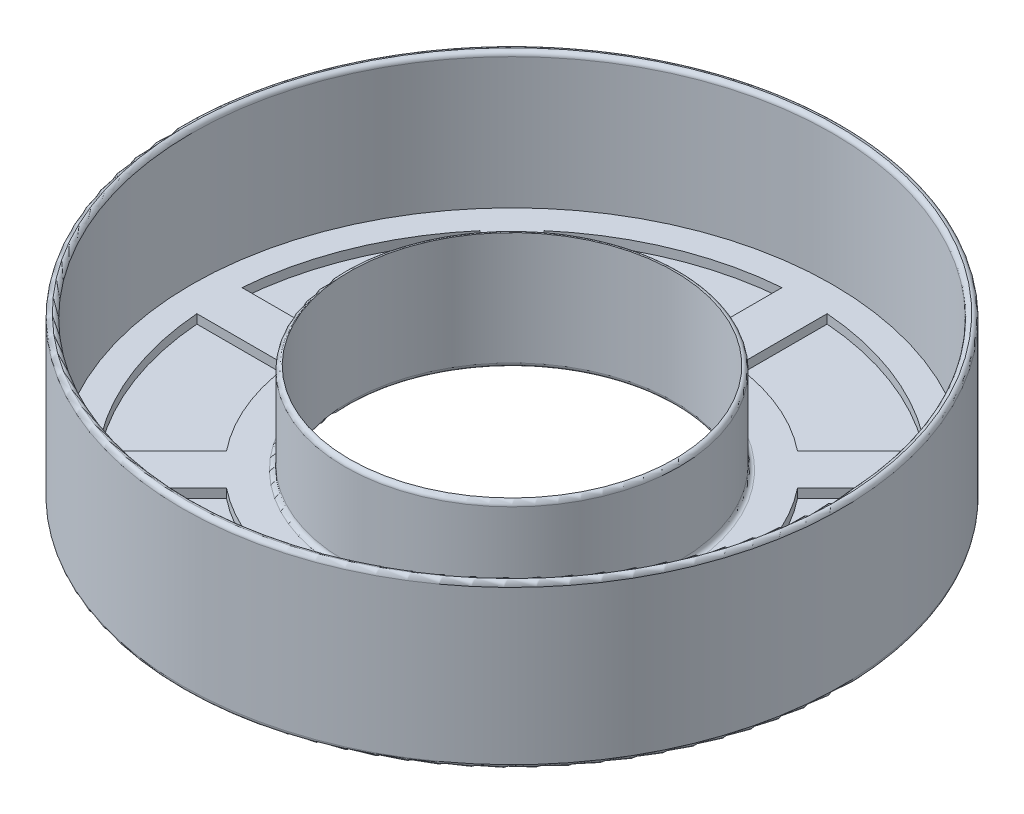
SolidWorks part; units mm, degrees
ref_plane "Front Plane" through (0, 0, 0) normal (0, 0, 1) x (1, 0, 0)
ref_plane "Top Plane" through (0, 0, 0) normal (0, 1, 0) x (1, 0, 0)
ref_plane "Right Plane" through (0, 0, 0) normal (1, 0, 0) x (0, 0, -1)
sketch "Sketch2" plane through (0, 0, 0) normal (0, 1, 0) x (1, 0, 0)
  circle A0 centre (0, 0) radius 18
  circle A1 centre (0, 0) radius 36.5
  dimension "D1" = 73
  dimension "D2" = 36
extrude "Boss-Extrude1" add sketch "Sketch2" along normal blind 3
sketch "Sketch3" plane through (0, 3, 0) normal (0, 1, 0) x (1, 0, 0)
  circle A0 centre (0, 0) radius 35.5
  circle A1 centre (0, 0) radius 19
  circle M3 centre (0, 0) radius 36.5
extrude "Boss-Extrude2" add sketch "Sketch3" along normal blind 15 contours A0 M3 region at (-36.3968, 3, 0)
sketch "Sketch4" plane through (0, 3, 0) normal (0, 1, 0) x (1, 0, 0)
  circle A0 centre (0, 0) radius 18.5
  circle M3 centre (0, 0) radius 18
extrude "Boss-Extrude3" add sketch "Sketch4" along normal blind 10 contours A0 M3 region at (-18.4477, 3, 0)
fillet "Fillet1" radius 0.5 6 edges at (0, 3, 18.5) (0, 13, 18.5) (0, 18, 35.5) (0, 18, 36.5) (0, 0, 18) (0, 0, 36.5)
sketch "Sketch5" plane through (0, 3, 0) normal (0, 1, 0) x (1, 0, 0)
  line L19 (14.0436, 17.5792) -> (21.1451, 24.6806)
  line L21 (-2.5, 22.3607) -> (-2.5, 32.4037)
  line L22 (-14.0436, 17.5792) -> (-21.1451, 24.6806)
  line L25 (-14.0436, -17.5792) -> (-21.1451, -24.6806)
  line L27 (2.5, -22.3607) -> (2.5, -32.4037)
  line L28 (14.0436, -17.5792) -> (21.1451, -24.6806)
  line L35 (-22.3607, -2.5) -> (-32.4037, -2.5)
  line L37 (22.3607, 2.5) -> (32.4037, 2.5)
  line L39 (24.6806, 21.1451) -> (17.5792, 14.0436)
  line L41 (32.4037, -2.5) -> (22.3607, -2.5)
  line L42 (2.5, 32.4037) -> (2.5, 22.3607)
  line L45 (-24.6806, 21.1451) -> (-17.5792, 14.0436)
  line L46 (-32.4037, 2.5) -> (-22.3607, 2.5)
  line L47 (15.9099, 15.9099) -> (22.981, 22.981)
  line L48 (-24.6806, -21.1451) -> (-17.5792, -14.0436)
  line L49 (-32.5, 0) -> (-22.5, 0) construction
  line L50 (-2.5, -32.4037) -> (-2.5, -22.3607)
  line L51 (22.5, 0) -> (32.5, 0) construction
  line L52 (24.6806, -21.1451) -> (17.5792, -14.0436)
  line L53 (-22.981, 22.981) -> (-15.9099, 15.9099)
  line L54 (0, 32.5) -> (0, 22.5) construction
  line L61 (-15.9099, -15.9099) -> (-22.981, -22.981)
  line L62 (0, -22.5) -> (0, -32.5) construction
  line L63 (15.9099, -15.9099) -> (22.981, -22.981)
  arc A2 (-2.5, 32.4037) -> (-21.1451, 24.6806) centre (0, 0) ccw
  arc A3 (-2.5, 22.3607) -> (-14.0436, 17.5792) centre (0, 0) ccw
  arc A8 (14.0436, 17.5792) -> (2.5, 22.3607) centre (0, 0) ccw
  arc A13 (21.1451, 24.6806) -> (2.5, 32.4037) centre (0, 0) ccw
  arc A14 (22.3607, 2.5) -> (17.5792, 14.0436) centre (0, 0) ccw
  arc A19 (32.4037, 2.5) -> (24.6806, 21.1451) centre (0, 0) ccw
  arc A20 (17.5792, -14.0436) -> (22.3607, -2.5) centre (0, 0) ccw
  arc A25 (24.6806, -21.1451) -> (32.4037, -2.5) centre (0, 0) ccw
  arc A26 (2.5, -22.3607) -> (14.0436, -17.5792) centre (0, 0) ccw
  arc A31 (2.5, -32.4037) -> (21.1451, -24.6806) centre (0, 0) ccw
  arc A32 (-14.0436, -17.5792) -> (-2.5, -22.3607) centre (0, 0) ccw
  arc A37 (-21.1451, -24.6806) -> (-2.5, -32.4037) centre (0, 0) ccw
  arc A38 (-32.4037, -2.5) -> (-24.6806, -21.1451) centre (0, 0) ccw
  arc A43 (-22.3607, -2.5) -> (-17.5792, -14.0436) centre (0, 0) ccw
  arc A44 (-24.6806, 21.1451) -> (-32.4037, 2.5) centre (0, 0) ccw
  arc A49 (-17.5792, 14.0436) -> (-22.3607, 2.5) centre (0, 0) ccw
extrude "Cut-Extrude1" cut sketch "Sketch5" against normal blind 1 contours A3 L21 A2 L22 | L19 A13 L42 A8 | L37 A19 L39 A14 | L52 A25 L41 A20 | A49 L45 A44 L46 | A43 L35 A38 L48 | L25 A37 L50 A32 | L27 A31 L28 A26 region at (10.5122, 3, -25.3786) region at (-10.5122, 3, -25.3786) region at (-10.5122, 3, 25.3786) region at (10.5122, 3, 25.3786) region at (-25.3786, 3, 10.5122) region at (25.3786, 3, -10.5122) region at (25.3786, 3, 10.5122) region at (-25.3786, 3, -10.5122)
